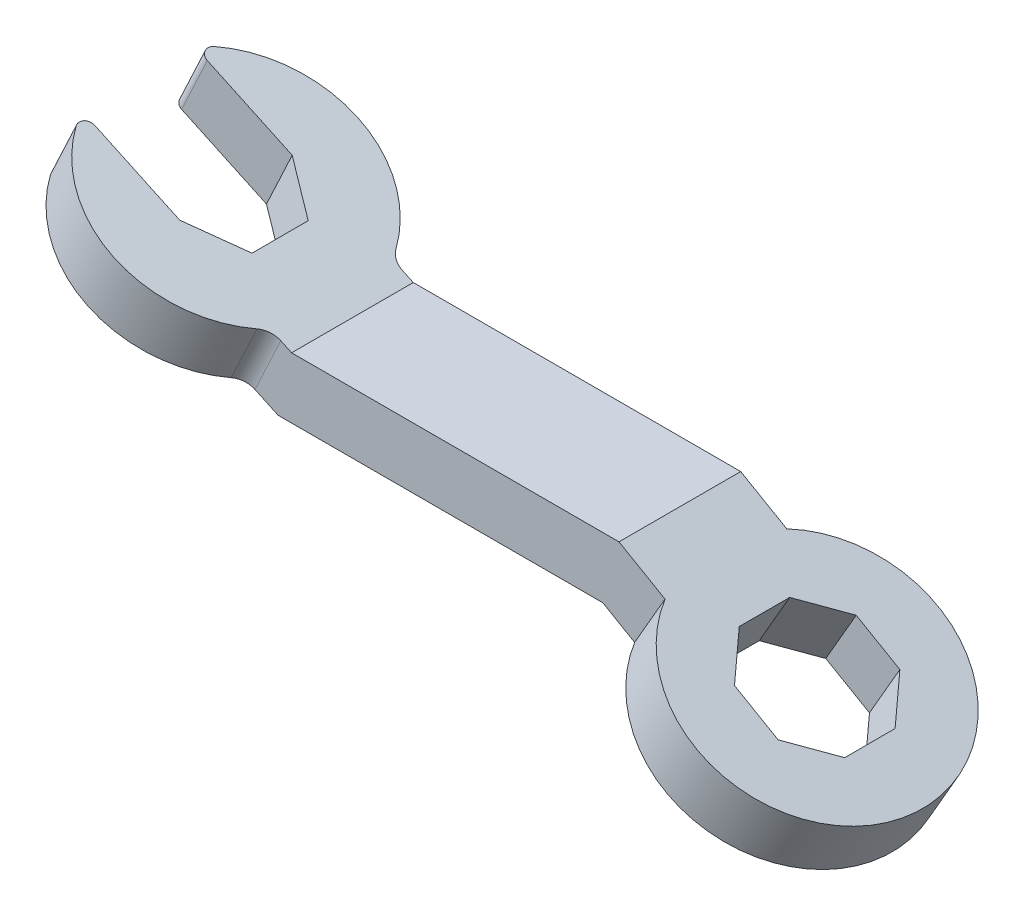
SolidWorks part; units mm, degrees
ref_plane "前视基准面" through (0, 0, 0) normal (0, 0, 1) x (1, 0, 0)
ref_plane "上视基准面" through (0, 0, 0) normal (0, 1, 0) x (1, 0, 0)
ref_plane "右视基准面" through (0, 0, 0) normal (1, 0, 0) x (0, 0, -1)
other "Configuration Table"
sketch "草图1" plane through (0, 0, 0) normal (0, 0, 1) x (1, 0, 0)
  line L0 (0, 0) -> (80, 0)
  line L1 (80, 0) -> (106.8301, -15.4904)
  line L2 (106.8301, -15.4904) -> (114.3301, -2.5)
  line L3 (114.3301, -2.5) -> (84.0192, 15)
  line L4 (84.0192, 15) -> (3.3254, 15)
  line L5 (3.3254, 15) -> (-25.3815, 28.3863)
  line L6 (-25.3815, 28.3863) -> (-31.7208, 14.7916)
  line L7 (0, 0) -> (-31.7208, 14.7916)
  dimension "D1" = 15
  dimension "D2" = 25
  dimension "D3" = 80
  dimension "D4" = 15
  dimension "D5" = 15
  dimension "D6" = 30
  dimension "D7" = 35
  dimension "D8" = 35
extrude "凸台-拉伸1" add sketch "草图1" along normal mid plane 30
sketch "草图3" plane through (27.5, 47.6314, 0) normal (0.5, 0.866, 0) x (0.866, -0.5, 0)
  line L0 (65.2628, 0) -> (131.7609, 0) construction
  line L1 (65.2628, -15) -> (65.2628, 15) construction
  line L11 (119.3453, -6.2132) -> (119.3453, 6.2132)
  line L12 (119.3453, 6.2132) -> (110.5585, 15)
  line L13 (110.5585, 15) -> (98.1321, 15)
  line L14 (98.1321, 15) -> (89.3453, 6.2132)
  line L15 (89.3453, 6.2132) -> (89.3453, -6.2132)
  line L16 (89.3453, -6.2132) -> (98.1321, -15)
  line L17 (98.1321, -15) -> (110.5585, -15)
  line L18 (110.5585, -15) -> (119.3453, -6.2132)
  circle A0 centre (104.3453, 0) radius 30
  circle A1 centre (104.3453, 0) radius 15 construction
  dimension "D1" = 60
  dimension "D2" = 30
extrude "切除-拉伸1" cut sketch "草图3" against normal through all both and the other way through all contours A0 | L11 L12 L13 L14 L15 L16 L17 L18
extrude "凸台-拉伸2" add sketch "草图3<3>" against normal up to surface (15 mm away) up to face at (83.0627, -1.7682, 0)
sketch "草图3<3>" plane through (27.5, 47.6314, 0) normal (0.5, 0.866, 0) x (0.866, -0.5, 0) same geometry as "草图3"
ref_plane "基准面1" through (0, 0, -15) normal (0.9063, -0.4226, 0) x (0, 0, -1)
sketch "草图6" plane through (0, 0, 0) normal (-0.4226, -0.9063, 0) x (0.9063, -0.4226, 0)
  line L0 (-35, 15) -> (-35, -15) construction
  line L1 (-35, 13.8564) -> (-61.6083, 13.8564)
  line L2 (-23, 6.9282) -> (-35, 13.8564)
  line L5 (-35, -15) -> (0, -15)
  line L6 (0, -15) -> (0, 15)
  line L7 (0, 15) -> (-35, 15)
  line L8 (-35, 15) -> (-35, -15)
  line L9 (-9.0192, -15) -> (0, -15)
  line L10 (0, -15) -> (0, 15)
  line L11 (0, 15) -> (-9.0192, 15)
  line L14 (-35, -13.8564) -> (-23, -6.9282)
  line L15 (-23, -6.9282) -> (-23, 6.9282)
  line L16 (-35, -13.8564) -> (-61.6083, -13.8564)
  line L18 (-47, 0) -> (-47, -6.9282) [skipped]
  line L19 (-47, -6.9282) -> (-41, -10.3923) [skipped]
  line L20 (-35, 13.8564) -> (-41, 10.3923) [skipped]
  arc A0 (-61.6083, -13.8564) -> (-61.6083, 13.8564) centre (-35, 0) ccw
  arc A2 (-29, -10.3923) -> (-29, 10.3923) centre (-35, 0) ccw construction
  line M12 (-35, -15) -> (0, -15)
  line M14 (0, 15) -> (-35, 15)
  line M15 (-35, 15) -> (-35, -15)
  dimension "D1" = 60
  dimension "D2" = 0
extrude "凸台-拉伸3" add sketch "草图6" along direction (-0.4226, -0.9063, 0) on the side against the normal blind 15 contours A0 L1 M14 M15 | A0 L2 L15 L14 M12 M14 M15 | L16 A0 M12 M15 region at (-15.3522, 7.1588, 0) region at (-32.3358, 15.0784, 20.8036) region at (-32.3358, 15.0784, -20.8036)
extrude "切除-拉伸2" cut sketch "草图6<4>" against normal through all both and the other way through all contours L14 L15 L2 M15 region at (-26.8871, 12.5377, 0)
sketch "草图6<4>" plane through (0, 0, 0) normal (-0.4226, -0.9063, 0) x (0.9063, -0.4226, 0) same geometry as "草图6"
fillet "圆角1" radius 5 2 edges at (-5.0046, 10.609, -15) (-5.0046, 10.609, 15)
fillet "圆角2" radius 2 2 edges at (-52.6664, 32.8341, -13.8564) (-52.6664, 32.8341, 13.8564)
